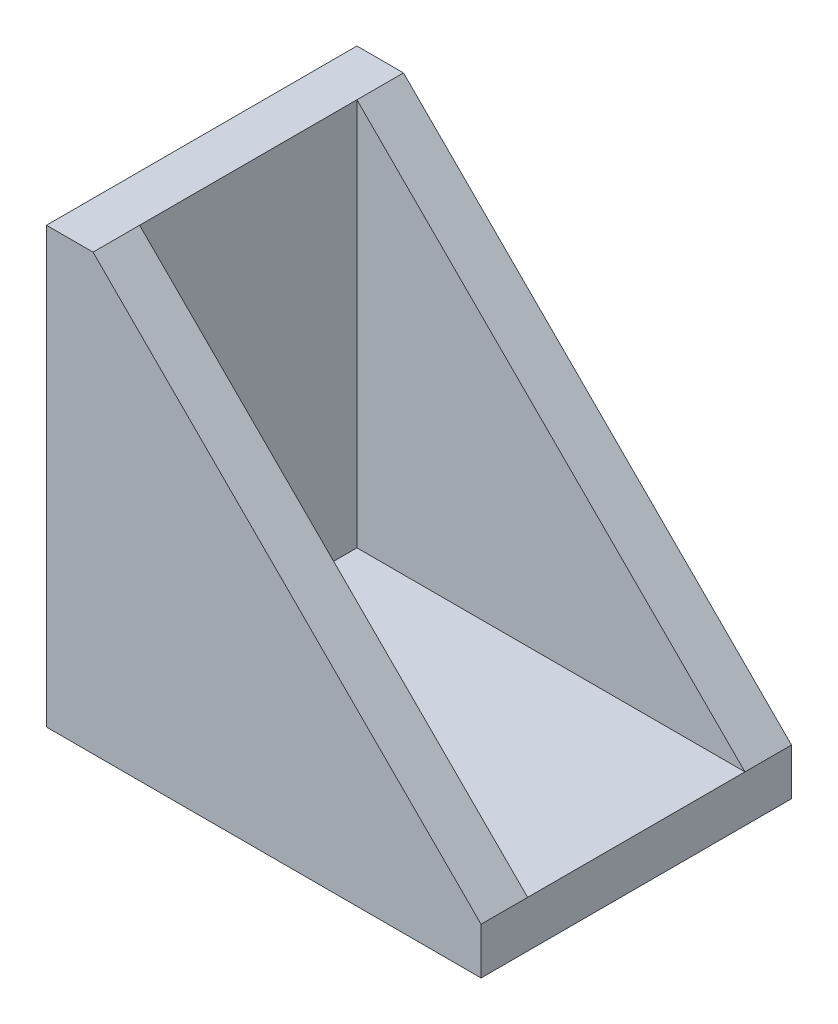
SolidWorks part; units mm, degrees
material "356.0-T6 Permanent Mold cast (SS)"
ref_plane "Front Plane" through (0, 0, 0) normal (0, 0, 1) x (1, 0, 0)
ref_plane "Top Plane" through (0, 0, 0) normal (0, 1, 0) x (1, 0, 0)
ref_plane "Right Plane" through (0, 0, 0) normal (1, 0, 0) x (0, 0, -1)
sketch "Sketch1" plane through (0, 0, 0) normal (0, 0, 1) x (1, 0, 0)
  line L0 (28, 0) -> (0, 0)
  line L1 (0, 0) -> (0, 28)
  line L2 (0, 28) -> (3, 28)
  line L3 (3, 28) -> (28, 3)
  line L4 (28, 3) -> (28, 0)
  dimension "D1" = 28
  dimension "D2" = 3
extrude "Body" add sketch "Sketch1" along normal mid plane 20
shell "Shell" thickness 3 removed face at (15.5, 15.5, 0) removed face at (1.5, 28, 0) removed face at (28, 1.5, 0)
